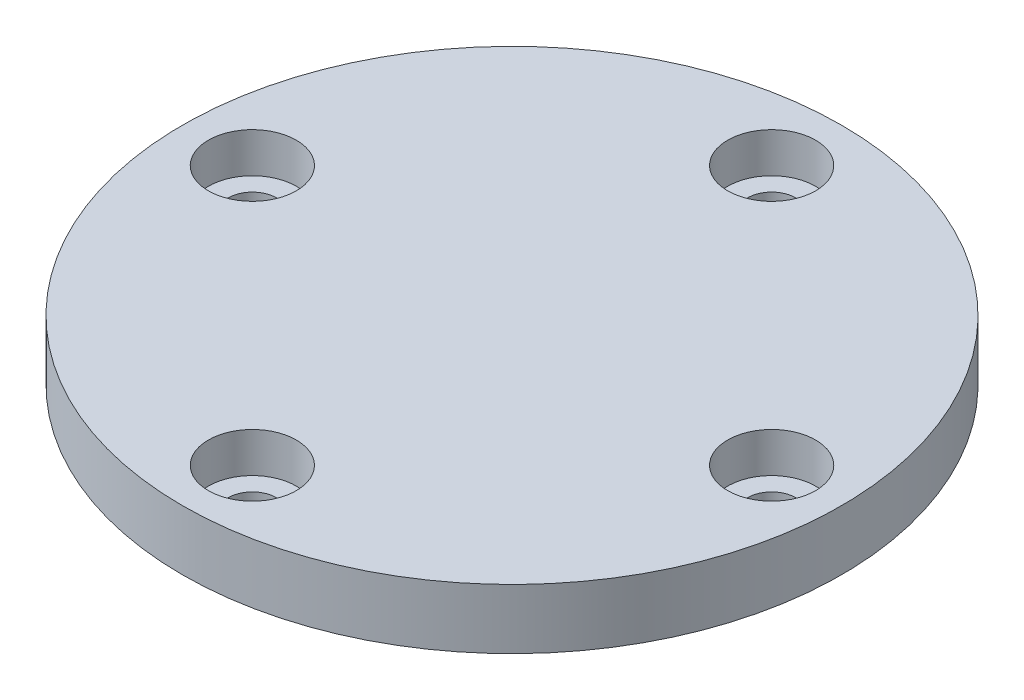
SolidWorks part; units mm, degrees
material "1060 Alloy"
ref_plane "Front Plane" through (0, 0, 0) normal (0, 0, 1) x (1, 0, 0)
ref_plane "Top Plane" through (0, 0, 0) normal (0, 1, 0) x (1, 0, 0)
ref_plane "Right Plane" through (0, 0, 0) normal (1, 0, 0) x (0, 0, -1)
sketch "Sketch1" plane through (0, 0, 0) normal (0, 1, 0) x (1, 0, 0)
  circle A0 centre (0, 0) radius 16.5
  dimension "D1" = 33
extrude "Boss-Extrude1" add sketch "Sketch1" along normal blind 3
sketch "Sketch3" plane through (0, 3, 0) normal (0, 1, 0) x (1, 0, 0)
  circle A0 centre (0, -10.25) radius 0.25
  circle A1 centre (0, 0) radius 9.8
  dimension "D1" = 0.5
  dimension "D2" = 10.25
  dimension "D3" = 19.6
sketch "Sketch4" plane through (0, 3, 0) normal (0, -1, 0) x (1, 0, 0)
  line L0 (0, 0) -> (13.2597, 13.2597) construction
  circle A0 centre (7.7782, 7.7782) radius 1
  dimension "D2" = 2
  dimension "D1" = 11
sketch "Sketch5" plane through (0, 3, 0) normal (0, 1, 0) x (1, 0, 0)
  circle A0 centre (0, 0) radius 11
  dimension "D1" = 22
hole_wizard "CBORE for M2 SHCS1" positions "Sketch6" profile "Sketch7" counterbore size "M2" standard "ANSI Metric" end condition through all
sketch "Sketch6" plane through (0, 3, 0) normal (0, 1, 0) x (1, 0, 0)
  point P0 (13, 0)
  dimension "D1" = 13
sketch "Sketch7" plane through (13, 3, 0) normal (1, 0, 0) x (0, 0, 1)
  line L0 (0, 0) -> (0, 3)
  line L1 (0, 3) -> (1.2, 3)
  line L3 (1.2, 3) -> (1.2, 2)
  line L4 (1.2, 2) -> (2.2, 2)
  line L5 (2.2, 2) -> (2.2, 0)
  line L7 (2.2, 0) -> (0, 0)
  line L11 (0, -6.35) -> (0, 107.95) construction
  dimension "Thru Hole Dia." = 2.4
  dimension "Thru Hole Depth" = 3
  dimension "C'Bore Dia." = 4.4
  dimension "C'Bore Depth" = 2
pattern_circular "CirPattern1" count 4 over 360 about axis through (0, 3, 0) along (0, 1, 0) of "CBORE for M2 SHCS1"
sketch "Sketch8" plane through (0, 0, 0) normal (0, -1, 0) x (1, 0, 0)
  circle A0 centre (0, 0) radius 9
  dimension "D1" = 18
extrude "Boss-Extrude2" add sketch "Sketch8" along normal blind 2
